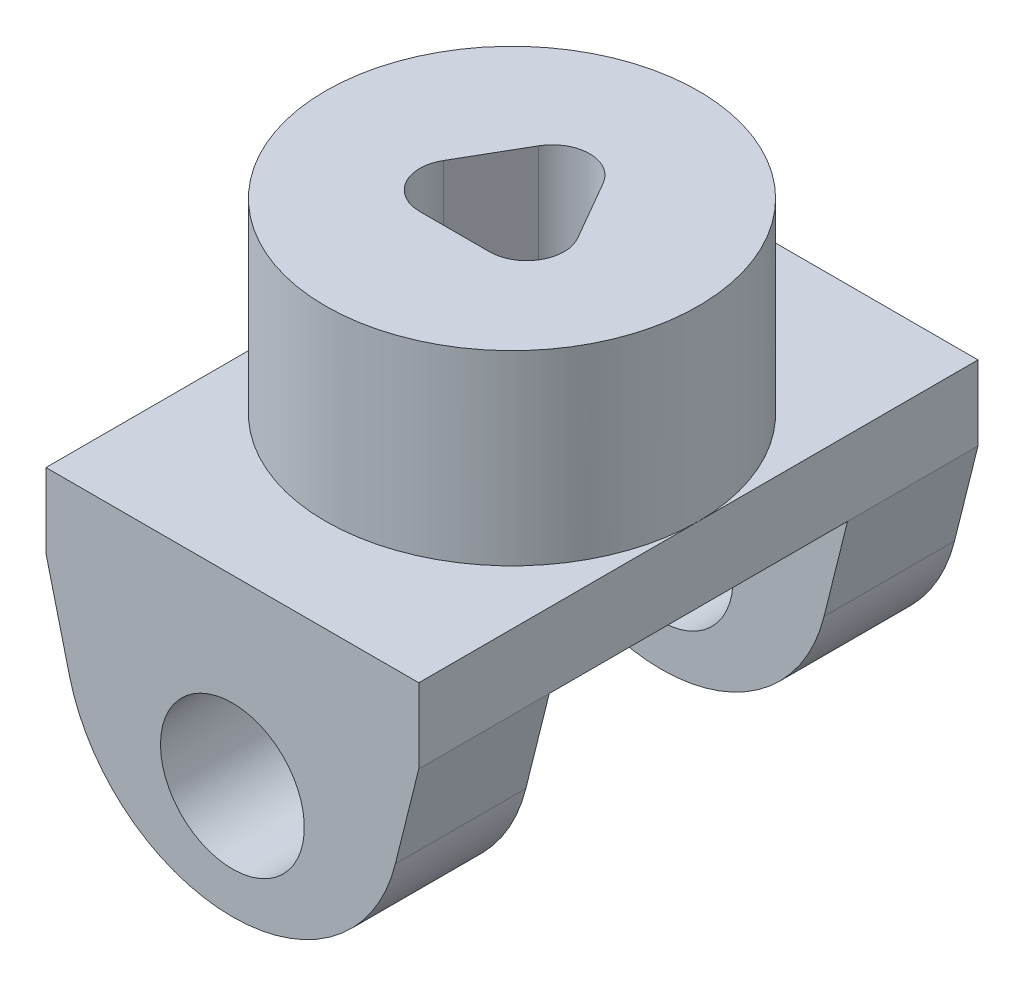
SolidWorks part; units mm, degrees
ref_plane "Front Plane" through (0, 0, 0) normal (0, 0, 1) x (1, 0, 0)
ref_plane "Top Plane" through (0, 0, 0) normal (0, 1, 0) x (1, 0, 0)
ref_plane "Right Plane" through (0, 0, 0) normal (1, 0, 0) x (0, 0, -1)
sketch "Sketch1" plane through (0, 0, 0) normal (0, 1, 0) x (1, 0, 0)
  line L1 (-6.35, -9.525) -> (6.35, -9.525)
  line L2 (-6.35, -9.525) -> (-6.35, 9.525)
  line L3 (-6.35, 9.525) -> (6.35, 9.525)
  line L4 (6.35, -9.525) -> (6.35, 9.525)
  line L5 (-6.35, -9.525) -> (6.35, 9.525) construction
  line L6 (-6.35, 9.525) -> (6.35, -9.525) construction
  circle A0 centre (0, 0) radius 6.35
  point P0 (0, 0)
extrude "Boss-Extrude1" add sketch "Sketch1" along normal blind 6.35 contours A0
extrude "Boss-Extrude3" add sketch "Sketch1<5>" against normal blind 10.16 contours L4 L3 L2 L1
sketch "Sketch1<5>" plane through (0, 0, 0) normal (0, 1, 0) x (1, 0, 0) same geometry as "Sketch1"
sketch "Sketch3" plane through (0, 6.35, 0) normal (0, 1, 0) x (1, 0, 0)
  line L0 (0, 2.5159) -> (-2.1789, -1.258) construction
  line L1 (-2.1789, -1.258) -> (2.1789, -1.258) construction
  line L2 (2.1789, -1.258) -> (0, 2.5159) construction
  line L3 (-1.0999, 2.0079) -> (-2.2888, -0.0515)
  line L4 (-1.189, -1.9565) -> (1.189, -1.9565)
  line L5 (2.2888, -0.0515) -> (1.0999, 2.0079)
  line L6 (3.3887, -1.9565) -> (0, 3.9129) construction
  line L7 (0, 3.9129) -> (-3.3887, -1.9565) construction
  line L8 (-3.3887, -1.9565) -> (3.3887, -1.9565) construction
  circle A0 centre (0, 0) radius 2.5159 construction
  arc A1 (1.0999, 2.0079) -> (-1.0999, 2.0079) centre (0, 1.3729) ccw
  arc A2 (-1.189, -1.9565) -> (-2.2888, -0.0515) centre (-1.189, -0.6865) cw
  arc A3 (2.2888, -0.0515) -> (1.189, -1.9565) centre (1.189, -0.6865) cw
  dimension "D1" = 60
  dimension "D5" = 1.27
  dimension "D6" = 1.27
  dimension "D7" = 1.27
  dimension "D2" = 60
  dimension "D3" = 3.7739
  dimension "D4" = 0.6985
extrude "Cut-Extrude1" cut sketch "Sketch3" against normal blind 7.62 contours A2 L3 A1 L5 A3 L4
sketch "Sketch5" plane through (0, 0, -9.525) normal (0, 0, -1) x (-1, 0, 0)
  line L0 (5.5512, -5.7439) -> (6.35, -2.54)
  line L1 (6.35, -10.16) -> (6.35, 0) construction
  line L2 (0, 9.0805) -> (0, -9.0805) construction
  line L3 (-5.5512, -5.7439) -> (-6.35, -2.54)
  circle A0 centre (0, -6.2198) radius 2.45
  arc A1 (-5.5512, -5.7439) -> (5.5512, -5.7439) centre (0, -4.3599) ccw
  dimension "D2" = 4.9
  dimension "D1" = 14
  dimension "D3" = 3.302
extrude "Cut-Extrude3" cut sketch "Sketch5" against normal through all and the other way through all contours L3 A1 L0
extrude "Cut-Extrude4" cut sketch "Sketch5<4>" against normal through all contours A0
sketch "Sketch5<4>" plane through (0, 0, -9.525) normal (0, 0, -1) x (-1, 0, 0) same geometry as "Sketch5"
sketch "Sketch6" plane through (0, 0, 0) normal (1, 0, 0) x (0, 0, -1)
  line L0 (-5.08, -2.54) -> (5.08, -2.54)
  line L1 (6.985, 0) -> (-6.985, 0) construction
  line L2 (-5.08, -2.54) -> (-5.08, -14.6532)
  line L3 (-5.08, -14.6532) -> (5.08, -14.6532)
  line L4 (5.08, -14.6532) -> (5.08, -2.54)
  dimension "D1" = 2.54
  dimension "D2" = 10.16
extrude "Cut-Extrude5" cut sketch "Sketch6" against normal through all and the other way through all
equation "\"D1@Boss-Extrude1\"=\"circle_length\""
equation "\"D1@Boss-Extrude3\"=\"extrusion_length\""
equation "\"D2@Sketch5\"=2*\"free_fit_bolt_radius\""
